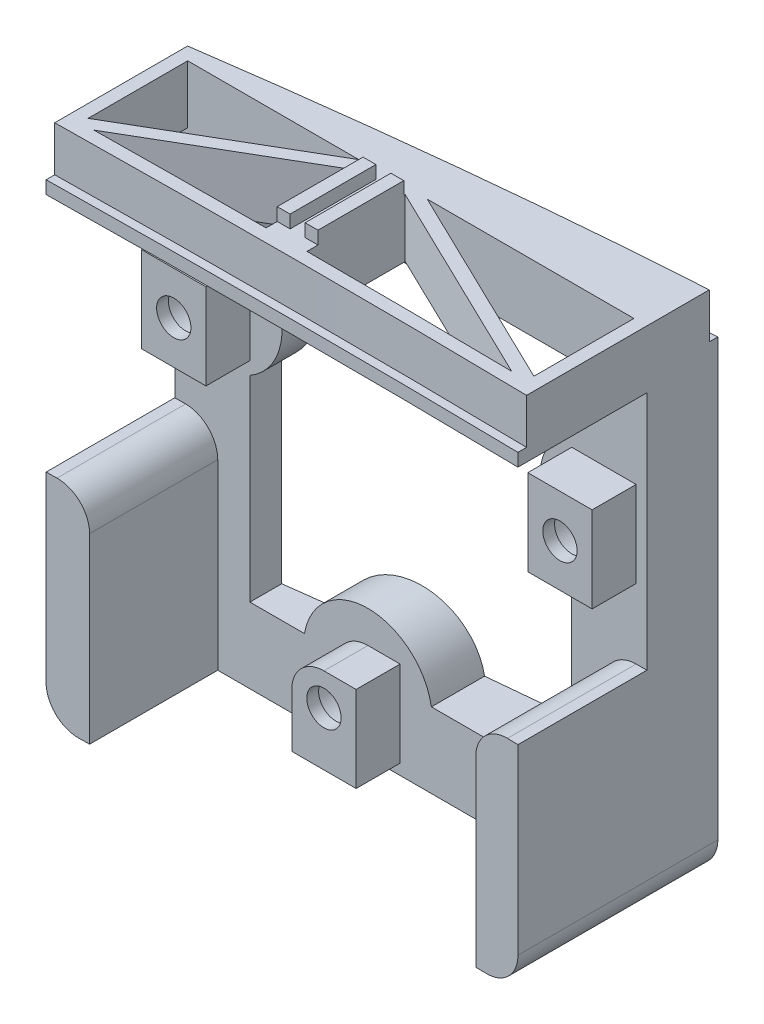
SolidWorks part; units mm, degrees
ref_plane "Front Plane" through (0, 0, 0) normal (0, 0, 1) x (1, 0, 0)
ref_plane "Top Plane" through (0, 0, 0) normal (0, 1, 0) x (1, 0, 0)
ref_plane "Right Plane" through (0, 0, 0) normal (1, 0, 0) x (0, 0, -1)
sketch "Sketch1" plane through (0, 0, 0) normal (0, 1, 0) x (1, 0, 0)
  line L0 (-144.1303, -12.9929) -> (155.8697, -12.8308) construction
  line L1 (-29.3738, 9.8314) -> (-29.3738, -4.1686)
  line L2 (14.6262, 14.4548) -> (14.6262, -4.183)
  line L5 (-29.3738, -2.9686) -> (14.6262, -2.9686)
  line L12 (-51.1303, 9.4041) -> (-59.1513, -7.7971) construction
  line L13 (-109.8536, -6.9996) -> (-109.986, -6.1605)
  line L14 (-11.0303, 7.0314) -> (-9.8303, 7.0314)
  line L15 (-11.0303, 7.0314) -> (-11.0303, -0.9686)
  line L16 (-11.0303, -0.9686) -> (-9.8303, -0.9686)
  line L17 (-9.8303, 7.0314) -> (-9.8303, -0.9686)
  line L18 (-8.4303, 7.0314) -> (-7.2303, 7.0314)
  line L19 (-8.4303, 7.0314) -> (-8.4303, -0.9686)
  line L20 (-8.4303, -0.9686) -> (-7.2303, -0.9686)
  line L21 (-7.2303, 7.0314) -> (-7.2303, -0.9686)
  circle A2 centre (-36.6303, 2.3202) radius 4.25
  arc A9 (-58.7697, -6.9788) -> (-58.7632, -6.9861) centre (-51.1303, -0.0856) ccw
  ellipse E0 centre (-36.6303, 2.3202) end of major axis (-36.1292, -4.0323) minor radius 5.05
  spline S0 degree 13 poles (-110.7235, -3.2524) (-98.8326, -0.2567) (-86.3944, 2.6358) (-73.4943, 5.427) (-60.2589, 8.0815) (-46.8275, 10.5453) (-33.3355, 12.7584) (-19.9065, 14.665) (-6.6486, 16.2187) (6.3449, 17.3865) (18.9944, 18.15) (31.2324, 18.5052) (43.0009, 18.4619) (54.25, 18.0415) knots 0.038912 0.038912 0.038912 0.038912 0.038912 0.038912 0.038912 0.038912 0.038912 0.038912 0.038912 0.038912 0.038912 0.038912 0.206425 0.206425 0.206425 0.206425 0.206425 0.206425 0.206425 0.206425 0.206425 0.206425 0.206425 0.206425 0.206425 0.206425
  spline S1 degree 3 poles (-105.7874, -5.9402) (-105.4515, -5.8576) (-103.7907, -5.4506) (-99.0842, -4.3142) (-91.5415, -2.5615) (-82.0457, -0.4684) (-69.1527, 2.2208) (-52.7063, 5.3568) (-32.7854, 8.6244) (-12.9944, 11.2716) (3.1558, 12.8711) (15.7533, 13.7541) (25.0163, 14.2135) (32.556, 14.4255) (38.4824, 14.4928) (41.3869, 14.4927) (42.8464, 14.4842) knots 0.043242 0.043242 0.043242 0.043242 0.044325 0.048583 0.058255 0.067926 0.077598 0.096941 0.116284 0.135628 0.154971 0.164642 0.174314 0.183986 0.188821 0.193657 0.193657 0.193657 0.193657
  spline S2 degree 3 poles (42.3412, -4.3021) (39.1703, -4.1474) (32.8439, -3.8739) (20.0493, -3.4589) (3.9637, -3.1861) (-15.3945, -3.1849) (-34.7131, -3.4228) (-53.9413, -3.8315) (-69.8279, -4.2978) (-82.3956, -4.7634) (-91.7251, -5.1693) (-99.1578, -5.5509) (-103.8174, -5.8207) (-105.4427, -5.9191) (-105.7874, -5.9402) knots 0.702444 0.702444 0.702444 0.702444 0.71714 0.731836 0.761227 0.790619 0.820011 0.849403 0.878795 0.89349 0.908186 0.922882 0.929138 0.930826 0.930826 0.930826 0.930826
  spline S3 degree 3 poles (-109.986, -6.1605) (-109.4642, -6.0291) (-108.4175, -5.7667) (-103.5943, -4.5692) (-94.8971, -2.4925) (-82.0108, 0.3758) (-63.7471, 4.1371) (-40.3543, 8.3552) (-16.9896, 11.6162) (1.2883, 13.4985) (14.7075, 14.5233) (27.7627, 15.1448) (36.8021, 15.2972) (42.0404, 15.2892) (43.1567, 15.2825) (43.6671, 15.2784) knots 0.038912 0.038912 0.038912 0.038912 0.040616 0.04232 0.054528 0.06816 0.081792 0.109056 0.13632 0.149952 0.163584 0.177216 0.190848 0.192861 0.194565 0.194565 0.194565 0.194565
  spline S4 degree 13 poles (52.5193, -8.6666) (40.2713, -7.9192) (27.7839, -7.3485) (15.1503, -6.9773) (2.4425, -6.804) (-10.2886, -6.8041) (-23.0116, -6.9375) (-35.7087, -7.1592) (-48.3688, -7.4339) (-60.9767, -7.7494) (-73.5011, -8.1244) (-85.8777, -8.6024) (-97.9897, -9.2254) (-109.6522, -9.993) knots 0.686195 0.686195 0.686195 0.686195 0.686195 0.686195 0.686195 0.686195 0.686195 0.686195 0.686195 0.686195 0.686195 0.686195 0.937578 0.937578 0.937578 0.937578 0.937578 0.937578 0.937578 0.937578 0.937578 0.937578 0.937578 0.937578 0.937578 0.937578
  spline S5 degree 3 poles (-110.5235, -4.0272) (-108.9029, -3.6189) (-105.6763, -2.8183) (-99.0735, -1.2268) (-90.6514, 0.7176) (-80.2925, 2.9758) (-67.9991, 5.4979) (-58.7506, 7.2436) (-50.652, 8.6798) (-47.6807, 9.1904) (-44.5606, 9.7093) (-38.2765, 10.745) (-25.0157, 12.7601) (-5.2278, 15.1631) (12.1229, 16.5847) (25.5727, 17.2429) (35.4177, 17.4948) (43.3901, 17.504) (49.633, 17.3925) (52.6803, 17.2987) (54.2127, 17.2415) knots 0.038912 0.038912 0.038912 0.038912 0.044146 0.049381 0.059851 0.07032 0.08079 0.096446 0.097403 0.1044 0.105092 0.106475 0.122668 0.143607 0.164546 0.175016 0.185486 0.195955 0.20119 0.206425 0.206425 0.206425 0.206425
  spline S6 degree 3 poles (52.5681, -7.868) (50.9024, -7.7664) (47.578, -7.5733) (40.8667, -7.2231) (32.4163, -6.8574) (22.195, -6.5335) (8.4979, -6.2488) (-8.6998, -6.1472) (-26.1679, -6.3047) (-37.8303, -6.5029) (-44.675, -6.6412) (-49.0049, -6.7375) (-53.5282, -6.8475) (-56.9797, -6.937) (-62.6027, -7.0912) (-70.3002, -7.3251) (-80.3346, -7.6831) (-90.3076, -8.1048) (-98.4897, -8.5174) (-104.9445, -8.8903) (-108.1134, -9.09) (-109.7048, -9.1947) knots 0.686195 0.686195 0.686195 0.686195 0.69405 0.701906 0.717617 0.733329 0.74904 0.780463 0.811886 0.82883 0.833892 0.843309 0.848739 0.854731 0.859237 0.874732 0.890444 0.906155 0.921867 0.929722 0.937578 0.937578 0.937578 0.937578
  spline S7 degree 3 poles (43.1189, -5.1414) (42.5664, -5.1139) (40.3515, -5.0059) (33.6908, -4.7068) (23.0612, -4.3421) (5.0464, -3.9837) (-17.5716, -3.9643) (-44.6283, -4.3923) (-66.9803, -4.9899) (-84.5965, -5.6437) (-96.3916, -6.1935) (-104.7586, -6.6717) (-108.8142, -6.9312) (-109.8536, -6.9996) knots 0.701175 0.701175 0.701175 0.701175 0.703751 0.711493 0.7321 0.752708 0.793923 0.835139 0.876354 0.896962 0.917569 0.932426 0.937578 0.937578 0.937578 0.937578
  spline S8 degree 3 poles (43.0791, -5.9404) (39.8994, -5.7822) (33.5559, -5.5021) (20.7207, -5.0752) (4.577, -4.7906) (-14.8622, -4.781) (-29.9542, -4.963) (-38.7515, -5.1226) (-41.4966, -5.1769) (-43.935, -5.226) (-46.8305, -5.2883) (-49.9812, -5.3611) (-51.9548, -5.4083) (-59.5635, -5.5969) (-69.6735, -5.894) (-82.18, -6.356) (-91.5501, -6.7627) (-99.2415, -7.157) (-105.3139, -7.5106) (-108.2984, -7.6991) (-109.7967, -7.7977) knots 0.701175 0.701175 0.701175 0.701175 0.71595 0.730726 0.760276 0.789826 0.819377 0.829214 0.830132 0.831967 0.840401 0.843428 0.846456 0.849484 0.878477 0.893252 0.908028 0.922803 0.93019 0.937578 0.937578 0.937578 0.937578
  spline S9 degree 3 poles (-110.1814, -5.3848) (-108.6794, -5.0063) (-105.6878, -4.2632) (-99.5742, -2.785) (-91.7846, -0.9758) (-82.2124, 1.1324) (-69.613, 3.7573) (-59.5108, 5.6872) (-50.135, 7.3499) (-46.7114, 7.9355) (-40.1955, 9.0106) (-29.5503, 10.6773) (-12.6029, 12.9298) (3.6765, 14.5228) (16.3735, 15.3941) (25.7087, 15.8415) (33.3064, 16.0409) (39.2778, 16.0967) (42.204, 16.0903) (43.6745, 16.0785) knots 0.038912 0.038912 0.038912 0.038912 0.043776 0.04864 0.058368 0.068097 0.077825 0.096092 0.09776 0.105207 0.106069 0.116738 0.136195 0.155652 0.16538 0.175108 0.184837 0.189701 0.194565 0.194565 0.194565 0.194565
  dimension "D1" = 8.5
  dimension "D2" = 14
  dimension "D3" = 44
  dimension "D4" = 1.2
  dimension "D5" = 26.8
  dimension "D6" = 28.2
  dimension "D7" = 8
  dimension "D8" = 8
  dimension "D9" = 2
  dimension "D10" = 2
  dimension "D11" = 1.2
  dimension "D12" = 1.2
extrude "Boss-Extrude2" add sketch "Sketch1" against normal blind 47.8 contours S3 L1 S1 L2 | S1 L1 L5 L2 | S2 L2 L5 L1 | S7 L2 S2 L1 | L17 L14 L15 L16 | L21 L18 L19 L20 region at (-7.4038, 0, -12.035) region at (-6.1165, 0, -4.438) region at (-7.397, 0, 3.1176) region at (-7.3732, 0, 3.6567) region at (-10.4303, 0, -3.0314) region at (-7.8303, 0, -3.0314)
extrude "Cut-Extrude1" cut sketch "Sketch1<3>" against normal blind 4.2 contours S7 L2 S2 L1 | S3 L1 S1 L2 region at (-7.4038, 0, -12.035) region at (-7.3732, 0, 3.6567)
sketch "Sketch1<3>" plane through (0, 0, 0) normal (0, 1, 0) x (1, 0, 0) same geometry as "Sketch1"
sketch "Sketch2" plane through (0, 0, 0) normal (0, 1, 0) x (1, 0, 0)
  line L0 (-29.3738, 7.8314) -> (14.6262, 7.8314)
  line L1 (-29.3738, 9.8314) -> (-29.3738, -4.1686) construction
  line L2 (14.6262, 14.4548) -> (14.6262, -4.183) construction
  line L3 (-29.3738, -2.9686) -> (14.6262, -2.9686) construction
  line L4 (-29.3738, -2.9686) -> (14.6262, -2.9686)
  line L5 (14.6262, 14.4548) -> (14.6262, -4.183)
  line L6 (-29.3738, 9.8314) -> (-29.3738, -4.1686)
  spline S0 degree 3 poles (-1947.4588, -167.681) (424.4026, -117.2665) (271.9813, -15.4064) (33.6908, -4.7068) (23.0612, -4.3421) (5.0464, -3.9837) (-17.5716, -3.9643) (-44.6283, -4.3923) (-66.9803, -4.9899) (-84.5965, -5.6437) (-96.3916, -6.1935) (-281.2066, -16.7558) (-334.7502, -73.0291) (1880.8527, -187.1354) knots -0.374252 -0.374252 -0.374252 -0.374252 0.703751 0.711493 0.7321 0.752708 0.793923 0.835139 0.876354 0.896962 0.917569 0.932426 1.794118 1.794118 1.794118 1.794118 only from (43.1189, -5.1414) to (-109.8536, -6.9996) construction
  spline S1 degree 3 poles (43.1189, -5.1414) (42.5664, -5.1139) (40.3515, -5.0059) (33.6908, -4.7068) (23.0612, -4.3421) (5.0464, -3.9837) (-17.5716, -3.9643) (-44.6283, -4.3923) (-66.9803, -4.9899) (-84.5965, -5.6437) (-96.3916, -6.1935) (-104.7586, -6.6717) (-108.8142, -6.9312) (-109.8536, -6.9996) knots 0.701175 0.701175 0.701175 0.701175 0.703751 0.711493 0.7321 0.752708 0.793923 0.835139 0.876354 0.896962 0.917569 0.932426 0.937578 0.937578 0.937578 0.937578
  spline M3 degree 3 poles (-105.7874, -5.9402) (-105.4427, -5.9191) (-103.8174, -5.8207) (-99.1578, -5.5509) (-91.7251, -5.1693) (-82.3956, -4.7634) (-69.8279, -4.2978) (-53.9413, -3.8315) (-34.7131, -3.4228) (-15.3945, -3.1849) (3.9637, -3.1861) (20.0493, -3.4589) (32.8439, -3.8739) (39.1703, -4.1474) (42.3412, -4.3021) knots 0.702444 0.702444 0.702444 0.702444 0.704132 0.710388 0.725084 0.739779 0.754475 0.783867 0.813259 0.842651 0.872042 0.901434 0.91613 0.930826 0.930826 0.930826 0.930826 only from (-29.3738, -3.3687) to (14.6262, -3.383)
  line M4 (14.6262, -3.383) -> (14.6262, 13.6533)
  line M6 (-29.3738, 9.0233) -> (-29.3738, -3.3687)
  dimension "D1" = 2
extrude "Cut-Extrude2" cut sketch "Sketch2" against normal through all from offset 5.4 contours L4 L0 M6 M4 | L4 M6 M3 M4 | S1 L5 L6 M3 region at (-7.3738, 0, -2.4314) region at (-7.3795, 0, 3.5139) offset against normal yes
sketch "Sketch3" plane through (0, 0, -7.8314) normal (0, 0, 1) x (1, 0, 0)
  line L0 (14.6262, -47.8) -> (14.6262, -5.4) construction
  line L1 (-29.3738, -47.8) -> (14.6262, -47.8) construction
  circle A0 centre (-11.3738, -41.8) radius 2.5
  circle A1 centre (-25.3738, -17.3) radius 2.5
  circle A2 centre (10.6262, -17.3) radius 2.5
  dimension "D1" = 5
  dimension "D2" = 14
  dimension "D3" = 36
  dimension "D4" = 4
  dimension "D5" = 24.5
  dimension "D6" = 6
extrude "Cut-Extrude3" cut sketch "Sketch3" against normal through all
sketch "Sketch4" plane through (0, 0, -7.8314) normal (0, 0, 1) x (1, 0, 0)
  line L0 (-28.3738, -13.3) -> (-22.3738, -13.3)
  line L1 (-28.3738, -13.3) -> (-28.3738, -21.3)
  line L2 (-28.3738, -21.3) -> (-22.3738, -21.3)
  line L3 (-22.3738, -13.3) -> (-22.3738, -21.3)
  line L4 (7.6262, -13.3) -> (13.6262, -13.3)
  line L5 (7.6262, -13.3) -> (7.6262, -21.3)
  line L6 (7.6262, -21.3) -> (13.6262, -21.3)
  line L7 (13.6262, -13.3) -> (13.6262, -21.3)
  line L9 (-14.3738, -41.8) -> (-14.3738, -46.8)
  line L10 (-14.3738, -46.8) -> (-8.3738, -46.8)
  line L11 (-8.3738, -38.8) -> (-8.3738, -46.8)
  line L12 (-29.3738, -47.8) -> (-29.3738, -5.4) construction
  line L13 (14.6262, -47.8) -> (14.6262, -5.4) construction
  line L14 (-29.3738, -47.8) -> (14.6262, -47.8) construction
  line L15 (-11.3738, -38.8) -> (-8.3738, -38.8)
  arc A0 (-11.3738, -38.8) -> (-14.3738, -41.8) centre (-11.3738, -41.8) ccw
  point P23 (-25.3738, -21.3)
  dimension "D11" = 28.5
  dimension "D12" = 3
  dimension "D1" = 1
  dimension "D2" = 8
  dimension "D3" = 6
  dimension "D4" = 6
  dimension "D5" = 8
  dimension "D6" = 1
  dimension "D7" = 1
  dimension "D8" = 8
  dimension "D9" = 6
  dimension "D10" = 14
extrude "Boss-Extrude4" add sketch "Sketch4" along normal blind 4.1
sketch "Sketch8" plane through (0, 0, -7.8314) normal (0, 0, 1) x (1, 0, 0)
  circle A0 centre (10.6262, -17.3) radius 1.6
  circle A1 centre (-25.3738, -17.3) radius 1.6
  circle A2 centre (-11.3738, -41.8) radius 1.6
  dimension "D1" = 3.2
extrude "Cut-Extrude6" cut sketch "Sketch8" against normal through all both and the other way through all
ref_plane "Plane3" through (0, 0, -4.8314) normal (0, 0, 1) x (1, 0, 0)
ref_plane "Plane1" through (0, 0, -8.0314) normal (0, 0, 1) x (1, 0, 0)
sketch "Sketch9" plane through (0, 0, -8.0314) normal (0, 0, 1) x (1, 0, 0)
  circle A0 centre (10.6262, -17.3) radius 2.5
  circle A1 centre (-25.3738, -17.3) radius 2.5
  circle A2 centre (-11.3738, -41.8) radius 2.5
  dimension "D1" = 5
ref_plane "Plane2" through (0, 0, -9.0314) normal (0, 0, 1) x (1, 0, 0)
sketch "Sketch10" plane through (0, 0, -9.0314) normal (0, 0, 1) x (1, 0, 0)
  circle A0 centre (10.6262, -17.3) radius 2.7
  circle A1 centre (-11.3738, -41.8) radius 2.7
  circle A2 centre (-25.3738, -17.3) radius 2.7
  dimension "D1" = 5.4
loft "Cut-Loft2" cut section "Sketch9" section "Sketch10" connector at (9.6622, -19.6067, -8.0314) connector at (10.8262, -19.9926, -9.0314)
loft "Cut-Loft3" cut section "Sketch10<8>" section "Sketch9<8>" connector at (-23.8675, -15.0593, -9.0314) connector at (-23.8366, -15.3285, -8.0314)
sketch "Sketch10<8>" plane through (0, 0, -9.0314) normal (0, 0, 1) x (1, 0, 0) same geometry as "Sketch10"
sketch "Sketch9<8>" plane through (0, 0, -8.0314) normal (0, 0, 1) x (1, 0, 0) same geometry as "Sketch9"
loft "Cut-Loft4" cut section "Sketch10<9>" section "Sketch9<9>" connector at (-9.5256, -39.8318, -9.0314) connector at (-9.7018, -39.9414, -8.0314)
sketch "Sketch10<9>" plane through (0, 0, -9.0314) normal (0, 0, 1) x (1, 0, 0) same geometry as "Sketch10"
sketch "Sketch9<9>" plane through (0, 0, -8.0314) normal (0, 0, 1) x (1, 0, 0) same geometry as "Sketch9"
sketch "Sketch12" plane through (0, 0, -4.8314) normal (0, 0, 1) x (1, 0, 0)
  circle A1 centre (-25.3738, -17.3) radius 2.5
  circle A2 centre (10.6262, -17.3) radius 2.5
  circle A3 centre (-11.3738, -41.8) radius 2.5
  dimension "D1" = 5
extrude "Cut-Extrude10" cut sketch "Sketch12" against normal through all
sketch "Sketch13" plane through (0, 0, -7.8314) normal (0, 0, 1) x (1, 0, 0)
  circle A0 centre (-25.3738, -17.3) radius 3
  circle A1 centre (10.6262, -17.3) radius 3
  circle A2 centre (-11.3738, -41.8) radius 3
  dimension "D1" = 6
extrude "Cut-Extrude11" cut sketch "Sketch13" against normal through all from surface starting at plane "Plane2"
sketch "Sketch14" plane through (0, 0, -7.8314) normal (0, 0, 1) x (1, 0, 0)
  line L0 (-22.3738, -21.3) -> (-22.3738, -13.3) construction
  line L1 (-22.3738, -6.2) -> (7.6262, -6.2)
  line L2 (-22.3738, -6.2) -> (-22.3738, -40.8)
  line L3 (-22.3738, -40.8) -> (7.6262, -40.8)
  line L4 (7.6262, -6.2) -> (7.6262, -40.8)
  line L6 (7.6262, -13.3) -> (7.6262, -21.3) construction
  line L7 (-29.3738, -5.4) -> (14.6262, -5.4) construction
  line L8 (-29.3738, -47.8) -> (14.6262, -47.8) construction
  circle A0 centre (-11.3738, -41.8) radius 6
  circle A1 centre (-25.3738, -17.3) radius 6
  circle A2 centre (10.6262, -17.3) radius 6
  dimension "D3" = 12
  dimension "D1" = 0.8
  dimension "D2" = 7
extrude "Cut-Extrude15" cut sketch "Sketch14" against normal through all contours A2 L4 L1 L2 A1 L3 A0 region at (-7.1859, -23.0743, -7.8314)
extrude "Boss-Extrude5" add sketch "Sketch1<4>" along normal blind 1.2 contours L17 L14 L15 L16 | L21 L18 L19 L20 region at (-10.4303, 0, -3.0314) region at (-7.8303, 0, -3.0314)
sketch "Sketch1<4>" plane through (0, 0, 0) normal (0, 1, 0) x (1, 0, 0) same geometry as "Sketch1"
sketch "Sketch16" plane through (0, 0, 0) normal (0, 1, 0) x (1, 0, 0)
  line L0 (-29.3738, 7.8314) -> (14.6262, 7.8314) construction
  line L1 (-29.3738, 7.8314) -> (14.6262, 7.8314)
  line L2 (-28.1738, 7.8314) -> (-28.1738, -3.3521)
  line L3 (13.4262, 7.8314) -> (13.4262, -3.3616)
  line L4 (-29.3738, 9.0233) -> (-29.3738, -3.3687) construction
  line L5 (14.6262, 13.6533) -> (14.6262, -3.383) construction
  line L6 (-11.0303, 7.8314) -> (-11.0303, -2.0043)
  line L7 (-7.2303, 7.8314) -> (-7.2303, -1.9972)
  line L8 (-11.0303, 7.0314) -> (-11.0303, -0.9686) construction
  line L9 (-7.2303, 7.0314) -> (-7.2303, -0.9686) construction
  line L10 (-11.0303, 7.8314) -> (-28.1738, -2.152) construction
  line L11 (-7.2303, 7.8314) -> (13.4262, -2.1614) construction
  line L12 (-11.3322, 8.3499) -> (-28.4758, -1.6335)
  line L13 (-10.7284, 7.313) -> (-27.8719, -2.6705)
  line L14 (-7.4916, 7.2913) -> (13.1649, -2.7016)
  line L15 (-6.969, 8.3716) -> (13.6875, -1.6213)
  circle A0 centre (-11.0303, 7.8314) radius 0.6
  circle A1 centre (-7.2303, 7.8314) radius 0.6
  circle A2 centre (13.4262, -2.1614) radius 0.6
  circle A3 centre (-28.1738, -2.152) radius 0.6
  spline S0 degree 3 poles (-237.0475, -971.1944) (501.2171, -93.3247) (253.8045, -3.2026) (-320.3902, -3.1648) (-622.2406, -99.8928) (46.226, 993.7624) knots -0.40617 -0.40617 -0.40617 -0.40617 0.761227 0.790619 2.209243 2.209243 2.209243 2.209243 only from (14.6262, -3.383) to (-29.3738, -3.3687) construction
  spline S1 degree 3 poles (14.6262, -3.383) (11.0735, -3.3176) (1.077, -3.186) (-13.6131, -3.185) (-24.7175, -3.3027) (-29.3738, -3.3687) knots 0.744984 0.744984 0.744984 0.744984 0.761227 0.790619 0.811897 0.811897 0.811897 0.811897
  spline S2 degree 1 poles (14.6482, -2.1832) (-29.3908, -2.1688) knots 0 0 1 1 construction
  spline S3 degree 3 poles (14.6482, -2.1832) (14.3424, -2.1776) (13.8336, -2.1684) (10.1691, -2.1054) (3.5012, -2.0233) (-3.6044, -1.9952) (-7.8637, -1.9974) (-9.1304, -1.9994) (-10.397, -2.0022) (-13.4845, -2.0121) (-19.4178, -2.0479) (-24.9153, -2.1078) (-28.5796, -2.1575) (-29.0863, -2.1645) (-29.3908, -2.1688) knots 0.744984 0.744984 0.744984 0.744984 0.746379 0.747309 0.761712 0.776781 0.779665 0.781107 0.78255 0.785434 0.795169 0.809581 0.810507 0.811897 0.811897 0.811897 0.811897
  line M7 (-7.2303, 7.0314) -> (-7.2303, -0.9686)
  line M18 (-11.0303, -0.9686) -> (-11.0303, 7.0314)
  dimension "D4" = 1.2
  dimension "D1" = 1.2
  dimension "D2" = 1.2
  dimension "D3" = 1.2
  dimension "D5" = 0.6
  dimension "D6" = 0.6
  dimension "D7" = 0.6
  dimension "D8" = 0.6
extrude "Cut-Extrude16" cut sketch "Sketch16" against normal up to surface (5.4 mm away) contours L12 L1 L2 | S3 L6 L13 M18 | S3 L14 L7 M7 | L1 L15 L3 region at (-22.8567, 0, -4.7351) region at (-16.3308, 0, -1.0076) region at (6.9999, 0, -4.7227) region at (-0.8392, 0, -1.0275) up to face at (-1.8738, -5.4, -3.326)
sketch "Sketch17" plane through (0, -5.4, 0) normal (0, -1, 0) x (1, 0, 0)
  line L1 (-29.3738, -7.8314) -> (-25.3738, -7.8314)
  line L2 (-29.3738, -7.8314) -> (-29.3738, 4.1686)
  line L4 (-25.3738, -7.8314) -> (-25.3738, 4.116)
  line L5 (14.6262, -7.8314) -> (10.6262, -7.8314)
  line L6 (14.6262, -7.8314) -> (14.6262, 4.183)
  line L8 (10.6262, -7.8314) -> (10.6262, 4.1171)
  spline S1 degree 3 poles (-1439.9508, 1327.7295) (571.77, 134.6459) (296.7394, 4.2338) (-397.6226, 3.6384) (-768.3734, 148.9839) (877.1569, -1722.2564) knots -0.596734 -0.596734 -0.596734 -0.596734 0.752708 0.793923 2.566496 2.566496 2.566496 2.566496 only from (14.6262, 4.183) to (-29.3738, 4.1686) construction
  spline S2 degree 3 poles (14.6262, 4.183) (12.9332, 4.1518) (2.2231, 3.9812) (-12.4727, 3.9686) (-25.4391, 4.1127) (-29.3738, 4.1686) knots 0.744962 0.744962 0.744962 0.744962 0.752708 0.793923 0.81191 0.81191 0.81191 0.81191
  line M5 (11.9997, 2.1379) -> (-7.2303, -7.1649)
  spline M7 degree 3 poles (14.6482, 2.1832) (14.3424, 2.1776) (13.8336, 2.1684) (10.1691, 2.1054) (3.5012, 2.0233) (-3.6044, 1.9952) (-7.8637, 1.9974) (-9.1304, 1.9994) (-10.397, 2.0022) (-13.4845, 2.0121) (-19.4178, 2.0479) (-24.9153, 2.1078) (-28.5796, 2.1575) (-29.0863, 2.1645) (-29.3908, 2.1688) knots 0.744984 0.744984 0.744984 0.744984 0.746379 0.747309 0.761712 0.776781 0.779665 0.781107 0.78255 0.785434 0.795169 0.809581 0.810507 0.811897 0.811897 0.811897 0.811897 only from (-7.2303, 1.9972) to (11.9997, 2.1379)
  line M8 (13.4262, 1.4949) -> (13.4262, -7.8314)
  line M9 (13.4262, -7.8314) -> (14.6262, -7.8314)
  line M10 (14.6262, -7.8314) -> (14.6262, 4.183)
  spline M11 degree 3 poles (43.1189, 5.1414) (42.5664, 5.1139) (40.3515, 5.0059) (33.6908, 4.7068) (23.0612, 4.3421) (5.0464, 3.9837) (-17.5716, 3.9643) (-44.6283, 4.3923) (-66.9803, 4.9899) (-84.5965, 5.6437) (-96.3916, 6.1935) (-104.7586, 6.6717) (-108.8142, 6.9312) (-109.8536, 6.9996) knots 0.701175 0.701175 0.701175 0.701175 0.703751 0.711493 0.7321 0.752708 0.793923 0.835139 0.876354 0.896962 0.917569 0.932426 0.937578 0.937578 0.937578 0.937578 only from (14.6262, 4.183) to (-29.3738, 4.1686)
  line M12 (-29.3738, 4.1686) -> (-29.3738, -7.8314)
  line M13 (-29.3738, -7.8314) -> (-28.1738, -7.8314)
  line M14 (-28.1738, -7.8314) -> (-28.1738, 1.4577)
  line M15 (-28.1738, 1.4577) -> (-12.2226, -7.8314)
  line M17 (-5.8525, -7.8314) -> (13.4262, 1.4949)
  line M19 (-11.0303, -7.1371) -> (-26.9538, 2.1358)
  spline M20 degree 3 poles (14.6482, 2.1832) (14.3424, 2.1776) (13.8336, 2.1684) (10.1691, 2.1054) (3.5012, 2.0233) (-3.6044, 1.9952) (-7.8637, 1.9974) (-9.1304, 1.9994) (-10.397, 2.0022) (-13.4845, 2.0121) (-19.4178, 2.0479) (-24.9153, 2.1078) (-28.5796, 2.1575) (-29.0863, 2.1645) (-29.3908, 2.1688) knots 0.744984 0.744984 0.744984 0.744984 0.746379 0.747309 0.761712 0.776781 0.779665 0.781107 0.78255 0.785434 0.795169 0.809581 0.810507 0.811897 0.811897 0.811897 0.811897 only from (-26.9538, 2.1358) to (-11.0303, 2.0043)
  dimension "D1" = 4
  dimension "D2" = 4
extrude "Boss-Extrude6" add sketch "Sketch17" against normal blind 20 from surface contours L1 L4 M15 M14 | L8 L5 M8 M17 | L4 M15 M19 M20 M11 M12 M13 M14 | L8 M17 M8 M9 M10 M11 M7 M5 | L8 M5 M7 | L4 M19 M20 region at (-29.2473, -5.4, -1.8314) region at (12.6283, -5.4, 4.0215) region at (-26.8187, -5.4, -3.5815) region at (12.0627, -5.4, -3.4981) starting at face at (-12.8738, -47.8, -10.4873)
fillet "Fillet1" radius 3 4 edges at (10.6262, -27.8, -1.8572) (-25.3738, -27.8, -1.8577)
sketch "Sketch19" plane through (14.6262, 0, 0) normal (1, 0, 0) x (0, 0, -1)
  line L0 (-2.983, -43.6) -> (-2.983, -29)
  line L1 (-2.983, -29) -> (5.2761, -43.6)
  line L2 (5.2761, -43.6) -> (-2.983, -43.6)
  line L3 (-1.6043, -29) -> (6.6548, -43.6)
  line L8 (-1.6043, -29) -> (6.6548, -29)
  line L9 (6.6548, -29) -> (6.6548, -43.6)
  line L10 (-4.183, -44.8) -> (14.4548, -44.8) construction
  line L11 (-4.183, -27.8) -> (-4.183, -44.8) construction
  line L12 (7.8314, -27.8) -> (-4.183, -27.8) construction
  line L14 (14.4548, -44.8) -> (14.4548, -4.2) construction
  dimension "D1" = 1.2
  dimension "D2" = 1.2
  dimension "D3" = 1.2
  dimension "D4" = 1.2
  dimension "D5" = 1.2
  dimension "D6" = 1.2
  dimension "D7" = 7.8
sketch "Sketch20" plane through (-29.3738, 0, 0) normal (-1, 0, 0) x (0, 0, 1)
  line L0 (-6.6314, -43.6) -> (-6.6314, -29)
  line L1 (-6.6314, -29) -> (1.5913, -43.6)
  line L2 (1.5913, -43.6) -> (-6.6314, -43.6)
  line L3 (-5.2542, -29) -> (2.9686, -43.6)
  line L8 (-5.2542, -29) -> (2.9686, -29)
  line L9 (2.9686, -29) -> (2.9686, -43.6)
  line L13 (4.1686, -27.8) -> (4.1686, -44.8) construction
  line L15 (4.1686, -27.8) -> (-7.8314, -27.8) construction
  line L17 (-9.8314, -44.8) -> (-9.8314, -4.2) construction
  line L18 (-9.8314, -44.8) -> (4.1686, -44.8) construction
  dimension "D1" = 1.2
  dimension "D2" = 1.2
  dimension "D3" = 1.2
  dimension "D4" = 3.2
  dimension "D5" = 1.2
  dimension "D6" = 1.2
  dimension "D7" = 1.2
